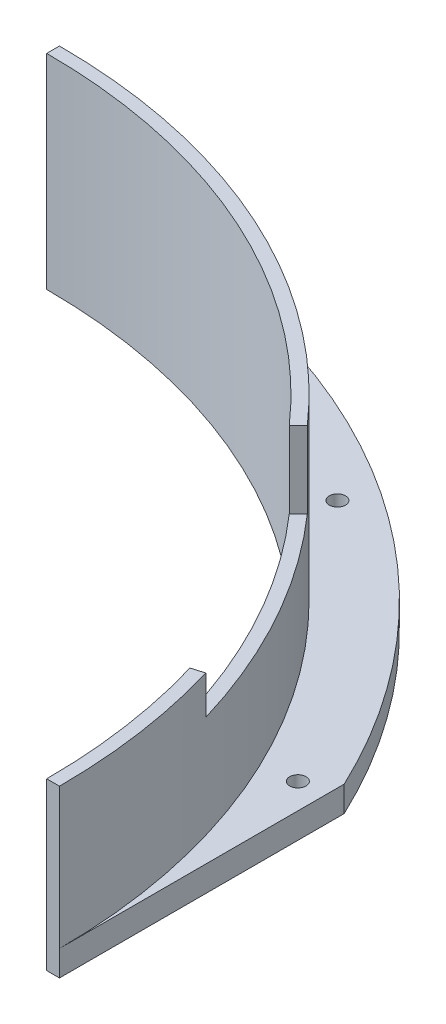
SolidWorks part; units mm, degrees
material "PET"
ref_plane "Front" through (0, 0, 0) normal (0, 0, 1) x (1, 0, 0)
ref_plane "Top" through (0, 0, 0) normal (0, 1, 0) x (1, 0, 0)
ref_plane "Right" through (0, 0, 0) normal (1, 0, 0) x (0, 0, -1)
sketch "Sketch1" plane through (0, 0, 0) normal (0, 1, 0) x (1, 0, 0)
  line L0 (0, 146.558) -> (0, 165.608)
  line L1 (-146.558, 0) -> (-165.608, 0)
  arc A0 (0, 146.558) -> (-146.558, 0) centre (0, 0) ccw
  arc A1 (0, 165.608) -> (-165.608, 0) centre (0, 0) ccw
  point P15 (0, 156.083)
  dimension "D2" = 146.558
  dimension "D1" = 19.05
extrude "Boss-Extrude1" add sketch "Sketch1" along normal blind 6.35 contours A0 L1 A1 L0
sketch "Sketch4" plane through (0, 6.35, 0) normal (0, 1, 0) x (1, 0, 0)
  line L2 (-149.733, 0) -> (-146.558, 0)
  line L3 (0, 146.558) -> (0, 149.733)
  line L4 (0, 146.558) -> (0, 165.608) construction
  arc A0 (-146.558, 0) -> (0, 146.558) centre (0, 0) cw
  arc A1 (0, 146.558) -> (-146.558, 0) centre (0, 0) ccw construction
  arc A2 (-149.733, 0) -> (0, 149.733) centre (0, 0) cw
  dimension "D1" = 3.175
extrude "Boss-Extrude2" add sketch "Sketch4" along normal blind 44.45
sketch "Sketch5" plane through (0, 50.8, 0) normal (0, 1, 0) x (1, 0, 0)
  line L0 (-105.8772, 105.8772) -> (-103.6322, 103.6322) construction
  line L1 (-146.558, 0) -> (-149.733, 0)
  line L2 (-112.398, 98.9276) -> (-110.1483, 96.6779)
  arc A0 (0, 149.733) -> (-149.733, 0) centre (0, 0) ccw construction
  arc A1 (0, 146.558) -> (-146.558, 0) centre (0, 0) ccw construction
  arc A2 (-110.1483, 96.6779) -> (-146.558, 0) centre (0, 0) ccw
  arc A3 (-112.398, 98.9276) -> (-149.733, 0) centre (0, 0) ccw
  dimension "D1" = 9.525
  dimension "D2" = 9.525
extrude "Cut-Extrude2" cut sketch "Sketch5" against normal blind 9.525 and the other way through all
sketch "Sketch7" plane through (0, 41.275, 0) normal (0, 1, 0) x (1, 0, 0)
  line L0 (-110.1483, 96.6779) -> (-112.398, 98.9276)
  line L1 (-137.1538, 51.6534) -> (-140.0886, 52.8691) construction
  line L2 (-143.5655, 42.5313) -> (-140.5213, 41.6294)
  line L4 (-112.398, 98.9276) -> (-110.1483, 96.6779) construction
  arc A0 (-140.5213, 41.6294) -> (-110.1483, 96.6779) centre (0, 0) cw
  arc A1 (-143.5655, 42.5313) -> (-112.398, 98.9276) centre (0, 0) cw
  arc A2 (-110.1483, 96.6779) -> (-146.558, 0) centre (0, 0) ccw construction
  arc A3 (-112.398, 98.9276) -> (-149.733, 0) centre (0, 0) ccw construction
  dimension "D1" = 6
extrude "Cut-Extrude3" cut sketch "Sketch7" against normal blind 9.525 and the other way through all from surface starting at face at (-134.1653, 41.275, -50.5813)
sketch "Sketch8" plane through (0, 6.35, 0) normal (0, 1, 0) x (1, 0, 0)
  line L1 (-149.733, 0) -> (-165.608, 0)
  line L2 (-149.733, 0) -> (-149.733, 76.2)
  line L3 (-149.733, 76.2) -> (-165.608, 76.2)
  line L4 (-165.608, 0) -> (-165.608, 76.2)
  dimension "D1" = 76.2
extrude "Cut-Extrude4" cut sketch "Sketch8" against normal through all
sketch "Sketch13" plane through (0, 6.35, 0) normal (0, 1, 0) x (1, 0, 0)
  line L0 (0, 149.733) -> (0, 165.608) construction
  line L1 (-143.383, 65.5843) -> (-87.8583, 130.9233) construction
  line L2 (-87.8583, 130.9233) -> (-6.35, 157.5426) construction
  line L4 (-149.733, 0) -> (-149.733, 70.7534) construction
  circle A0 centre (0, 0) radius 157.6705 construction
  point P0 (-6.35, 157.5426)
  point P2 (-87.8583, 130.9233)
  point P4 (-143.383, 65.5843)
  point P24 (0, 157.6705)
  dimension "D1" = 6.35
  dimension "D2" = 6.35
hole_wizard "#10-32 Tapped Hole1" positions "Sketch13" profile "Sketch12" tap size "#10-32" standard "ANSI Inch" end condition up to next
sketch "Sketch12" plane through (-6.35, 6.35, -157.5426) normal (1, 0, 0) x (0, 0, 1)
  line L0 (0, 0) -> (0, 6.35)
  line L1 (0, 6.35) -> (2.0193, 6.35)
  line L2 (2.0193, 6.35) -> (2.0193, 0)
  line L5 (2.0193, 0) -> (0, 0)
  line L11 (0, -6.35) -> (0, 107.95) construction
  dimension "Thru Tap Drill Dia." = 4.0386
  dimension "Thru Tap Drill Depth" = 6.35
cosmetic thread "Hole Thread1" parameters "D2"=4.826
cosmetic thread "Hole Thread2" parameters "D2"=4.826
cosmetic thread "Hole Thread3" parameters "D2"=4.826
mirror "Mirror2" about plane through (0, 0, 0) normal (1, 0, 0) of bodies 115
cosmetic thread "Hole Thread7" parameters "D2"=4.826
cosmetic thread "Hole Thread8" parameters "D2"=4.826
cosmetic thread "Hole Thread9" parameters "D2"=4.826
delete or keep bodies "Body-Delete/Keep 1" type delete bodies bodies 115
